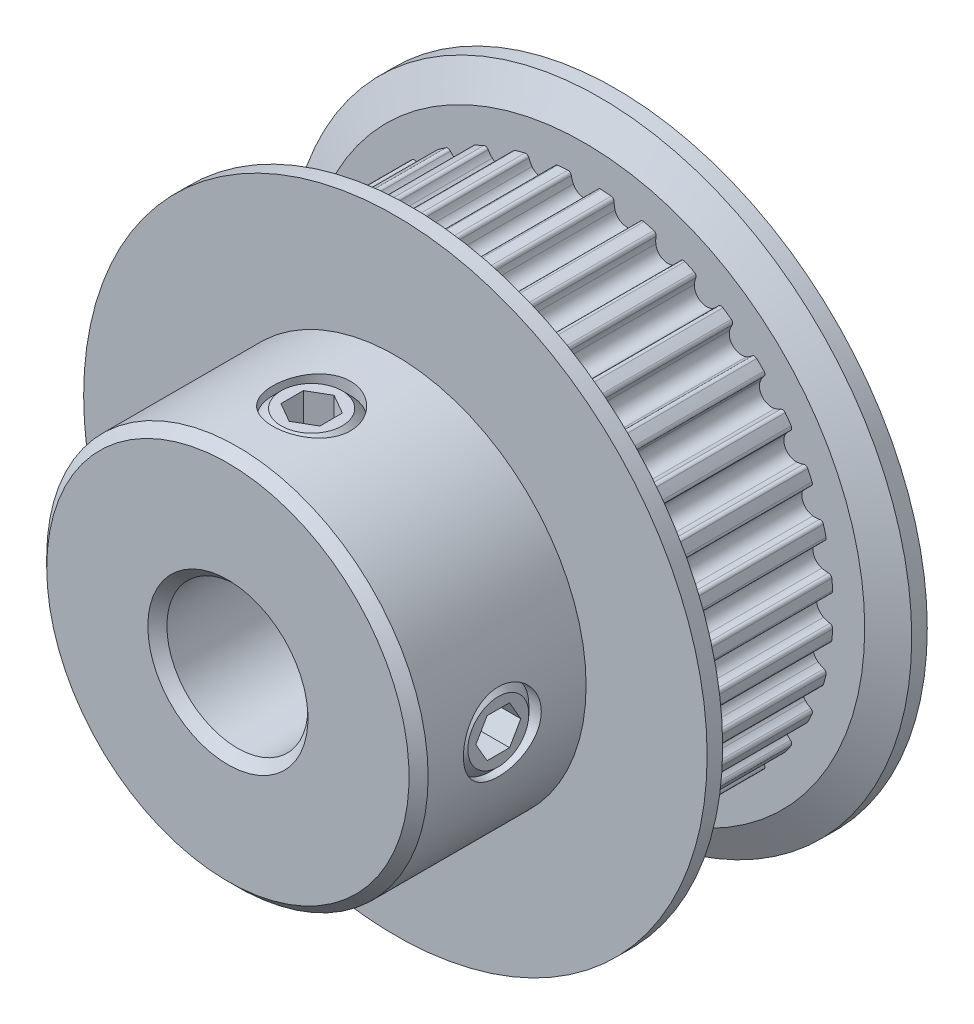
SolidWorks part; units mm, degrees
ref_plane "Front Plane" through (0, 0, 0) normal (0, 0, 1) x (1, 0, 0)
ref_plane "Top Plane" through (0, 0, 0) normal (0, 1, 0) x (1, 0, 0)
ref_plane "Right Plane" through (0, 0, 0) normal (1, 0, 0) x (0, 0, -1)
sketch "Sketch1" plane through (0, 0, 0) normal (0, 0, 1) x (1, 0, 0)
  line L1 (-1.8459, 10.4515) -> (1.8459, 10.4515) construction
  line L4 (0, 0) -> (0, 10.4515) construction
  line L5 (0, 10.4515) -> (0, 14.6067) construction
  line L6 (0, 11.4555) -> (1.9924, 11.2809) construction
  line L7 (1.9924, 11.2809) -> (2.8218, 11.1344) construction
  line L8 (1.9924, 11.2809) -> (1.8459, 10.4515) construction
  line L9 (-1.9924, 11.2809) -> (-1.8459, 10.4515) construction
  line L10 (-1.9482, 11.0308) -> (-2.4785, 14.0335)
  line L11 (-2.4785, 14.0335) -> (2.4785, 14.0335)
  line L12 (2.4785, 14.0335) -> (1.9482, 11.0308)
  circle A0 centre (0, 0) radius 11.4555 construction
  circle A1 centre (0, 0) radius 14.0335 construction
  circle A2 centre (0, 0) radius 11.2015 construction
  arc A3 (-0.4989, 10.7633) -> (0.4989, 10.7633) centre (0, 11.0065) ccw
  arc A4 (-0.4989, 10.7633) -> (-0.5884, 11.0497) centre (0.4, 11.2015) cw
  arc A5 (-1.9482, 11.0308) -> (-0.7467, 11.1766) centre (0, 0) cw
  arc A6 (-0.5884, 11.0497) -> (-0.7467, 11.1766) centre (-0.7367, 11.0269) ccw
  arc A7 (1.9482, 11.0308) -> (0.7467, 11.1766) centre (0, 0) ccw
  arc A8 (0.5884, 11.0497) -> (0.7467, 11.1766) centre (0.7367, 11.0269) cw
  arc A9 (0.4989, 10.7633) -> (0.5884, 11.0497) centre (-0.4, 11.2015) ccw
  point P6 (0, 20.9083)
  point P11 (0, 11.4555)
  point P13 (0, 14.0335)
  point P14 (0, 11.2015)
  dimension "D1" = 6.3016
  dimension "D2" = 3.1512
sketch "Sketch2" plane through (0, 0, 0) normal (1, 0, 0) x (0, 0, -1)
  line L0 (-8.7249, 3.175) -> (8.7249, 3.175)
  line L1 (-8.7249, 3.175) -> (-8.7249, 8.585)
  line L2 (-8.7249, 8.585) -> (-1.1851, 8.585)
  line L3 (-1.1851, 8.585) -> (-1.1851, 14.0335)
  line L4 (-1.1851, 14.0335) -> (0.2149, 14.0335) construction
  line L5 (0.2149, 14.0335) -> (0.2149, 11.2015) construction
  line L6 (0.2149, 11.2015) -> (7.3249, 11.2015)
  line L7 (7.3249, 11.2015) -> (7.3249, 14.0335) construction
  line L8 (7.3249, 14.0335) -> (8.7249, 14.0335) construction
  line L9 (8.7249, 14.0335) -> (8.7249, 3.175)
  line L10 (-8.7249, 0) -> (8.7249, 0) construction
  line L11 (8.0249, 14.0335) -> (7.3249, 12.6175)
  line L12 (0.2149, 12.6175) -> (-0.4851, 14.0335)
  line L13 (-1.1851, 14.0335) -> (-0.4851, 14.0335)
  line L14 (0.2149, 12.6175) -> (0.2149, 11.2015)
  line L15 (7.3249, 11.2015) -> (7.3249, 12.6175)
  line L16 (8.0249, 14.0335) -> (8.7249, 14.0335)
  arc A0 (0.2149, 12.6175) -> (-0.4851, 14.0335) centre (-1.5673, 12.6175) ccw construction
  arc A1 (7.3249, 12.6175) -> (8.0249, 14.0335) centre (9.1071, 12.6175) cw construction
  point P12 (0.2149, 12.6175)
  point P14 (-0.4851, 14.0335)
  point P20 (7.3249, 12.6175)
  point P21 (8.0249, 14.0335)
  point P25 (7.3249, 0)
  point P26 (0.2149, 0)
revolve "Revolve1" add sketch "Sketch2" angle 360 mid plane about L10
sketch "Sketch3" plane through (0, 0, 0) normal (0, 0, 1) x (1, 0, 0)
  line L6 (2.4785, 14.0335) -> (-2.4785, 14.0335)
  line L7 (1.9482, 11.0308) -> (2.4785, 14.0335)
  line L8 (-2.4785, 14.0335) -> (-1.9482, 11.0308)
  line L9 (2.4785, 14.0335) -> (-2.4785, 14.0335)
  line L10 (1.9482, 11.0308) -> (2.4785, 14.0335)
  line L11 (-2.4785, 14.0335) -> (-1.9482, 11.0308)
  arc A8 (1.9482, 11.0308) -> (0.7467, 11.1766) centre (0, 0) ccw
  arc A9 (0.7467, 11.1766) -> (0.5884, 11.0497) centre (0.7367, 11.0269) ccw
  arc A10 (0.4989, 10.7633) -> (0.5884, 11.0497) centre (-0.4, 11.2015) ccw
  arc A11 (-0.4989, 10.7633) -> (0.4989, 10.7633) centre (0, 11.0065) ccw
  arc A12 (-0.5884, 11.0497) -> (-0.4989, 10.7633) centre (0.4, 11.2015) ccw
  arc A13 (-0.5884, 11.0497) -> (-0.7467, 11.1766) centre (-0.7367, 11.0269) ccw
  arc A14 (-0.7467, 11.1766) -> (-1.9482, 11.0308) centre (0, 0) ccw
  arc A15 (1.9482, 11.0308) -> (0.7467, 11.1766) centre (0, 0) ccw
  arc A16 (0.7467, 11.1766) -> (0.5884, 11.0497) centre (0.7367, 11.0269) ccw
  arc A17 (0.4989, 10.7633) -> (0.5884, 11.0497) centre (-0.4, 11.2015) ccw
  arc A18 (-0.4989, 10.7633) -> (0.4989, 10.7633) centre (0, 11.0065) ccw
  arc A19 (-0.5884, 11.0497) -> (-0.4989, 10.7633) centre (0.4, 11.2015) ccw
  arc A20 (-0.5884, 11.0497) -> (-0.7467, 11.1766) centre (-0.7367, 11.0269) ccw
  arc A21 (-0.7467, 11.1766) -> (-1.9482, 11.0308) centre (0, 0) ccw
  dimension "D1" = 0
extrude "Cut-Extrude1" cut sketch "Sketch3" against normal up to vertex (7.3249 mm away) from vertex up to point (0, 11.2015, -7.3249) starting at point (0, 11.2015, -0.2149)
pattern_circular "CirPattern1" count 36 over 360 about axis through (0, 0, 8.7249) along (0, 0, 1) of "Cut-Extrude1"
sketch "Sketch4" plane through (0, 0, 0) normal (1, 0, 0) x (0, -1, 0)
  line L0 (0, -1.1851) -> (0, -8.7249) construction
  line L1 (-8.585, -1.1851) -> (8.585, -1.1851) construction
  line L2 (-8.585, -8.7249) -> (8.585, -8.7249) construction
  circle A0 centre (0, -4.955) radius 1.7526
extrude "Cut-Extrude2" cut sketch "Sketch4" along normal through all
ref_plane "Plane1" through (0, 0, 4.955) normal (0, 0, 1) x (1, 0, 0)
sketch "Sketch5" plane through (0, 0, 4.955) normal (0, 0, 1) x (1, 0, 0)
  line L0 (0, 0.1664) -> (0, 8.585) construction
  line L1 (3.175, -1.3716) -> (3.175, 0)
  line L2 (3.556, -1.7526) -> (8.0232, -1.7526)
  line L3 (3.175, 0) -> (8.585, 0) construction
  line L4 (3.175, 0) -> (8.4042, 0)
  line L5 (8.4042, 0) -> (8.4042, -1.3716)
  line L6 (3.556, -1.7526) -> (3.175, -1.3716)
  line L7 (8.4042, -1.3716) -> (8.0232, -1.7526)
  circle A0 centre (0, 0) radius 8.585 construction
  circle A1 centre (0, 0) radius 3.175 construction
  point P2 (3.175, -1.7526)
  point P11 (8.4042, -1.7526)
revolve "Revolve2" add sketch "Sketch5" angle 360 mid plane about L4
sketch "Sketch6" plane through (8.4042, 5.3841, 0) normal (-1, 0, 0) x (0, -1, 0)
  line L1 (5.3841, 5.9669) -> (4.5078, 5.4609)
  line L2 (4.5078, 5.4609) -> (4.5078, 4.4491)
  line L3 (4.5078, 4.4491) -> (5.3841, 3.9431)
  line L4 (5.3841, 3.9431) -> (6.2604, 4.4491)
  line L5 (6.2604, 4.4491) -> (6.2604, 5.4609)
  line L6 (6.2604, 5.4609) -> (5.3841, 5.9669)
  circle A0 centre (5.3841, 4.955) radius 0.8763 construction
  dimension "D1" = 1.7526
extrude "Cut-Extrude3" cut sketch "Sketch6" along normal blind 1.3144
pattern_circular "CirPattern2" count 2 over 90 about axis through (0, 0, 8.7249) along (0, 0, 1) of "Cut-Extrude2", "Revolve2", "Cut-Extrude3"
chamfer "Chamfer1" distance 0.4293 angle 45 2 edges at (3.175, 0, 8.7249) (8.585, 0, 8.7249)
ref_axis "Center Axis 1" through (0, 0, -8.7249) along (0, 0, 1)
ref_plane "Contact Plane 1" through (0, 0, 8.7249) normal (0, 0, 1) x (1, 0, 0)
ref_plane "Contact Plane 2" through (0, 0, -8.7249) normal (0, 0, -1) x (-1, 0, 0)
equation "\"D2@Sketch1\" = \"D1@Sketch1\"/2"
equation "\"D1@Sketch6\" = \"Set Screw@Sketch4\" / 2"
equation "\"D1@Cut-Extrude3\" = \"D1@Sketch6\"*.75"
equation "\"D1@Chamfer1\"=\"Hub Dia@Sketch2\"*.025"
